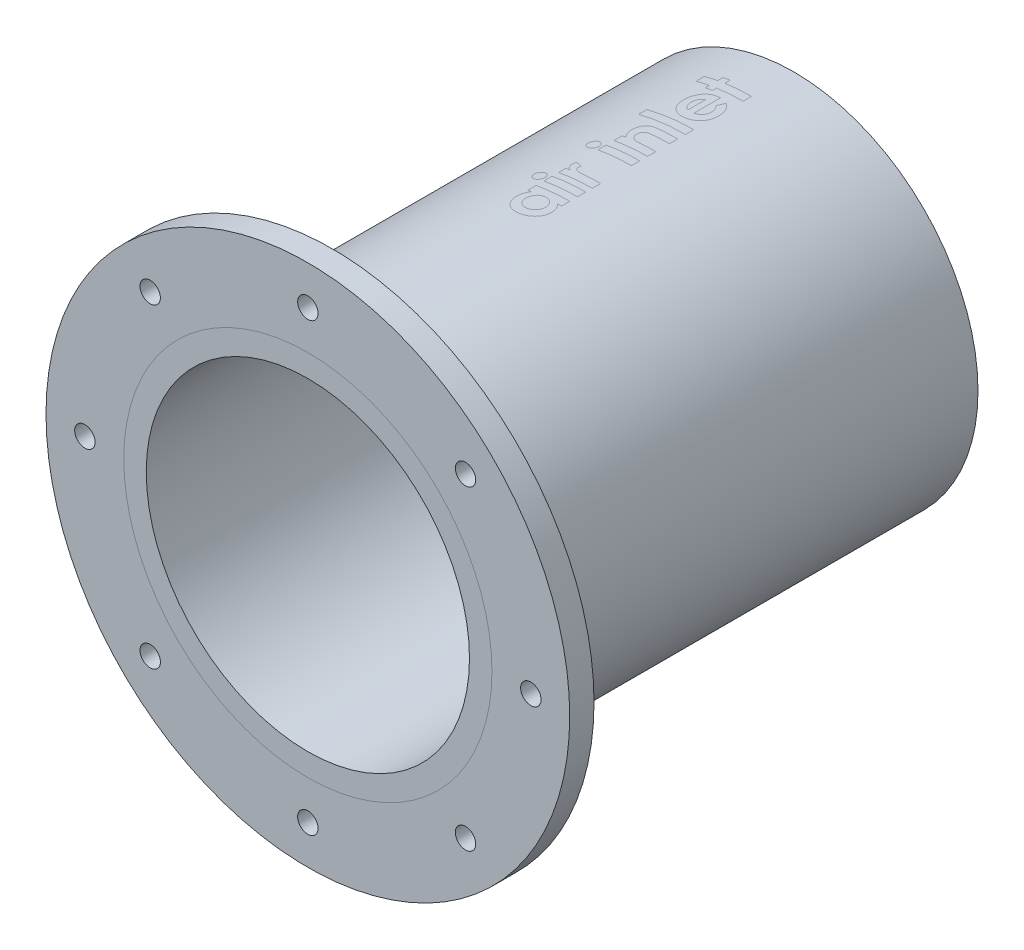
SolidWorks part; units mm, degrees
ref_plane "Front Plane" through (0, 0, 0) normal (0, 0, 1) x (1, 0, 0)
ref_plane "Top Plane" through (0, 0, 0) normal (0, 1, 0) x (1, 0, 0)
ref_plane "Right Plane" through (0, 0, 0) normal (1, 0, 0) x (0, 0, -1)
sketch "Sketch1" plane through (0, 0, 0) normal (0, 0, 1) x (1, 0, 0)
  circle A0 centre (0, 0) radius 37.875
  dimension "D1" = 75.75
extrude "Extrude-Thin1" add sketch "Sketch1" against normal blind 100 thin thin type one direction reverse wall 4.625
extrude "Extrude-Thin2" add sketch "Sketch1<2>" against normal blind 5 separate body thin thin type one direction wall 16
sketch "Sketch1<2>" plane through (0, 0, 0) normal (0, 0, 1) x (1, 0, 0) same geometry as "Sketch1"
hole_wizard "Ø4.2 (4.2) Diameter Hole1" positions "3DSketch4" profile "Sketch2" hole size "Ø4.2" standard "ISO" end condition through all
sketch3d "3DSketch4"
  line L1 (0, 0, 0) -> (0, 53.875, 0) construction
  circle A0 centre (0, 0, 0) radius 53.875 construction
  circle A1 centre (0, 0, 0) radius 53.875
  point P0 (0, 45.875, 0)
  point P10 (0, 0, 53.875)
  point P12 (0, 0, 53.875)
  dimension "D1" = 8
sketch "Sketch2" plane through (0, 45.875, 0) normal (1, 0, 0) x (0, -1, 0)
  line L0 (0, 0) -> (0, 100)
  line L1 (0, 100) -> (2.1, 100)
  line L2 (2.1, 100) -> (2.1, 0)
  line L5 (2.1, 0) -> (0, 0)
  line L11 (0, -6.35) -> (0, 107.95) construction
  dimension "Thru Hole Dia." = 4.2
  dimension "Thru Hole Depth" = 100
sketch "Sketch3" plane through (0, 0, 0) normal (0, 1, 0) x (1, 0, 0)
  line L1 (0, 100) -> (0, 40) construction
  line L2 (37.875, 100) -> (-37.875, 100) construction
  text T0 "<b>air inlet</b>\r\n" font "Century Gothic" height in points 36
  dimension "D1" = 60
wrap "Wrap1" sketch "Sketch3" wrap type scribe source sketch "Sketch3" face at (37.875, 0, -100)
pattern_circular "CirPattern5" count 8 over 360 about axis through (0, 0, -5) along (0, 0, 1) of "Ø4.2 (4.2) Diameter Hole1"
